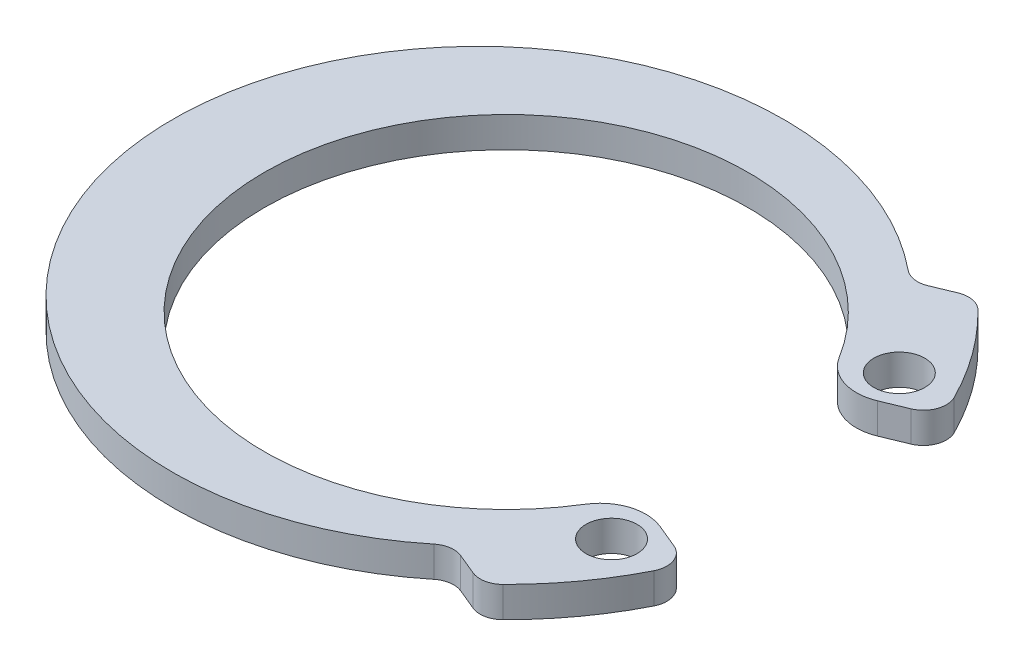
SolidWorks part; units mm, degrees
ref_plane "Front Plane" through (0, 0, 0) normal (0, 0, 1) x (1, 0, 0)
ref_plane "Top Plane" through (0, 0, 0) normal (0, 1, 0) x (1, 0, 0)
ref_plane "Right Plane" through (0, 0, 0) normal (1, 0, 0) x (0, 0, -1)
sketch "Sketch1" plane through (0, 0, 0) normal (0, 1, 0) x (1, 0, 0)
  line L0 (0, 0) -> (2.8916, 3.7684) construction
  line L1 (2.8916, 3.7684) -> (3.9874, 5.1965) construction
  line L2 (0, 0) -> (4.3884, 1.8177) construction
  line L3 (4.3884, 1.8177) -> (6.0514, 2.5066) construction
  line L4 (0, 0) -> (4.3884, -1.8177) construction
  line L5 (4.3884, -1.8177) -> (6.0514, -2.5066) construction
  line L6 (0, 0) -> (2.8916, -3.7684) construction
  line L7 (2.8916, -3.7684) -> (3.9874, -5.1965) construction
  line L8 (5.0194, -3.8515) -> (0, 0) construction
  line L9 (0, 0) -> (6.55, 0) construction
  line L10 (6.0514, 2.5066) -> (6.0514, -2.5066) construction
  line L11 (6.0514, -2.5066) -> (3.9874, -5.1965) construction
  line L12 (6.0514, 2.5066) -> (3.9874, 5.1965) construction
  line L13 (5.0194, 3.8515) -> (0, 0) construction
  line L14 (-4.75, 0) -> (-6.55, 0) construction
  circle A0 centre (0, 0) radius 6.55 construction
  circle A1 centre (0, 0) radius 4.75 construction
  arc A4 (5.2199, 2.1622) -> (4.4824, 3.4395) centre (0, 0) ccw construction
  arc A7 (5.2199, -2.1622) -> (4.4824, -3.4395) centre (0, 0) cw construction
  circle A8 centre (4.893, -2.825) radius 0.5 construction
  circle A9 centre (4.893, 2.825) radius 0.5 construction
  point P20 (6.0514, 0)
  dimension "Ring OD" = 13.1
  dimension "R" = 1
  dimension "D1" = 30
  dimension "D3" = 45
  dimension "S" = 1.8
sketch "Sketch2" plane through (0, 0, 0) normal (1, 0, 0) x (0, 0, -1)
  line L3 (6.55, 0) -> (-6.55, 0) construction
  line L7 (6.55, 0.3) -> (6.55, -0.3) construction
  dimension "Ring Thickness" = 0.6
sketch "Sketch3" plane through (0, 0, 0) normal (0, 1, 0) x (1, 0, 0)
  line L1 (-6.55, 0) -> (-4.75, 0) construction
  line L2 (4.3884, -1.8177) -> (6.0514, -2.5066) construction
  line L3 (2.8916, -3.7684) -> (3.9874, -5.1965) construction
  line L5 (3.6937, 4.5877) -> (4.1099, 4.7601)
  line L6 (5.1533, 2.1346) -> (5.6203, 2.328)
  line L7 (5.1533, -2.1346) -> (5.6203, -2.328)
  line L8 (3.6937, -4.5877) -> (4.1099, -4.7601)
  line L9 (2.8916, 3.7684) -> (3.9874, 5.1965) construction
  line L10 (4.3884, 1.8177) -> (6.0514, 2.5066) construction
  line L11 (0, 0) -> (4.3884, 1.8177) construction
  arc A1 (4.0428, 2.4936) -> (4.0428, -2.4936) centre (0, 0) ccw
  circle A2 centre (0, 0) radius 4.75 construction
  arc A3 (3.2374, 4.6544) -> (3.2374, -4.6544) centre (-0.5496, 0) ccw
  circle A4 centre (0, 0) radius 6.55 construction
  arc A6 (4.598, 4.6649) -> (5.85, 2.9462) centre (0, 0) cw
  arc A7 (4.1099, -4.7601) -> (4.598, -4.6649) centre (4.2821, -4.3444) ccw
  arc A8 (4.598, -4.6649) -> (5.85, -2.9462) centre (0, 0) ccw
  circle A9 centre (4.893, -2.825) radius 0.5
  circle A10 centre (4.893, 2.825) radius 0.5
  circle A11 centre (4.893, 2.825) radius 0.5 construction
  circle A12 centre (4.893, -2.825) radius 0.5 construction
  arc A13 (3.2374, -4.6544) -> (3.6937, -4.5877) centre (3.5215, -5.0035) cw
  arc A14 (5.6203, -2.328) -> (5.85, -2.9462) centre (5.4481, -2.7438) cw
  arc A15 (5.1533, -2.1346) -> (4.0428, -2.4936) centre (4.8089, -2.966) ccw
  arc A16 (5.1533, 2.1346) -> (4.0428, 2.4936) centre (4.8089, 2.966) cw
  arc A17 (5.6203, 2.328) -> (5.85, 2.9462) centre (5.4481, 2.7438) ccw
  arc A18 (4.1099, 4.7601) -> (4.598, 4.6649) centre (4.2821, 4.3444) cw
  arc A19 (3.2374, 4.6544) -> (3.6937, 4.5877) centre (3.5215, 5.0035) ccw
  arc A20 (5.2199, 2.1622) -> (4.4824, 3.4395) centre (0, 0) ccw construction
  arc A21 (4.4824, -3.4395) -> (5.2199, -2.1622) centre (0, 0) ccw construction
  point P24 (3.4395, 4.4824)
  point P30 (3.4395, -4.4824)
  dimension "D1" = 0.45
  dimension "D2" = 0.9
extrude "Boss-Extrude1" add sketch "Sketch3" along normal up to vertex (0.3 mm away) and the other way up to vertex (0.3 mm away) up to point (0, 0.3, -6.55) other way up to point (0, -0.3, -6.55)
sketch "Sketch4" plane through (0, 0, 0) normal (0, 1, 0) x (1, 0, 0)
  line L0 (0, -5.9752) -> (0, 5.9752) construction
  arc A0 (3.2374, 4.6544) -> (3.2374, -4.6544) centre (-0.5496, 0) ccw construction
  point P7 (0, 0)
  point P9 (0, -5.9752)
equation "\"D1@Sketch3\"=\"S@Sketch1\"/4"
equation "\"D2@Sketch3\"=\"S@Sketch1\"/2"
